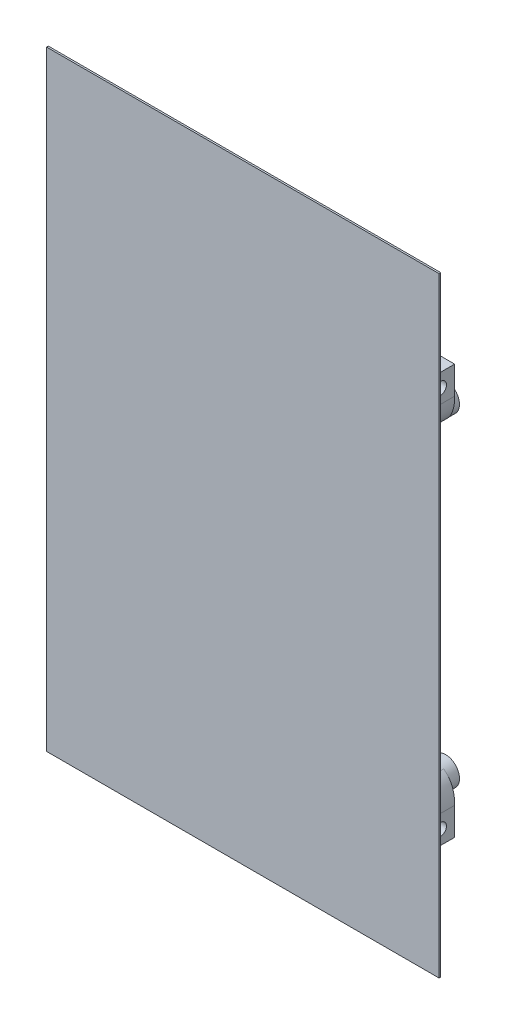
SolidWorks part; units mm, degrees
ref_plane "Front Plane" through (0, 0, 0) normal (0, 0, 1) x (1, 0, 0)
ref_plane "Top Plane" through (0, 0, 0) normal (0, 1, 0) x (1, 0, 0)
ref_plane "Right Plane" through (0, 0, 0) normal (1, 0, 0) x (0, 0, -1)
sketch "Sketch1" plane through (0, 0, 0) normal (0, 0, 1) x (1, 0, 0)
  line L1 (109, 161.3091) -> (-4, 161.3091)
  line L2 (109, 161.3091) -> (109, -14.3091)
  line L3 (109, -14.3091) -> (-4, -14.3091)
  line L4 (-4, 161.3091) -> (-4, -14.3091)
extrude "Boss-Extrude1" add sketch "Sketch1" along normal blind 0.5
sketch "Sketch2" plane through (0, 0, 0) normal (0, 0, -1) x (-1, 0, 0)
  circle A0 centre (-5.6, 26.85) radius 2 construction
  circle A1 centre (-99.4, 26.85) radius 2 construction
  circle A2 centre (-99.4, 120.15) radius 2 construction
  circle A3 centre (-5.6, 120.15) radius 2 construction
  circle A4 centre (-5.6, 26.85) radius 2
  circle A5 centre (-99.4, 26.85) radius 2
  circle A6 centre (-99.4, 120.15) radius 2
  circle A7 centre (-5.6, 120.15) radius 2
  circle A8 centre (-5.6, 120.15) radius 4
  circle A9 centre (-5.6, 26.85) radius 4
  circle A10 centre (-99.4, 26.85) radius 4
  circle A11 centre (-99.4, 120.15) radius 4
  dimension "D1" = 8
extrude "Boss-Extrude2" add sketch "Sketch2" along normal up to surface (11 mm away)
sketch "Sketch3" plane through (0, 0, 0) normal (0, 0, -1) x (-1, 0, 0)
  line L0 (-99.4, 120.15) -> (-5.6, 120.15) construction
  line L1 (-7.3321, 123.15) -> (-8.2458, 123.15)
  line L2 (-9.0641, 120.15) -> (-7.3321, 117.15)
  line L3 (-7.3321, 117.15) -> (-3.8679, 117.15)
  line L4 (-3.8679, 117.15) -> (-2.1359, 120.15)
  line L5 (-2.1359, 120.15) -> (-3.8679, 123.15)
  line L6 (-3.8679, 123.15) -> (-7.3321, 123.15)
  line L7 (-7.3321, 123.15) -> (-9.0641, 120.15)
  line L8 (-7.3321, 117.15) -> (-8.2458, 117.15)
  line L9 (-52.5, 161.3091) -> (-52.5, -14.3091) construction
  line L10 (-109, 161.3091) -> (4, 161.3091) construction
  line L11 (4, -14.3091) -> (-109, -14.3091) construction
  line L12 (-97.6679, 117.15) -> (-96.7542, 117.15)
  line L13 (-97.6679, 123.15) -> (-95.9359, 120.15)
  line L14 (-95.9359, 120.15) -> (-97.6679, 117.15)
  line L15 (-97.6679, 117.15) -> (-101.1321, 117.15)
  line L16 (-101.1321, 117.15) -> (-102.8641, 120.15)
  line L17 (-102.8641, 120.15) -> (-101.1321, 123.15)
  line L18 (-101.1321, 123.15) -> (-97.6679, 123.15)
  line L19 (-97.6679, 123.15) -> (-96.7542, 123.15)
  line L20 (-109, 73.5) -> (4, 73.5) construction
  line L21 (-109, -14.3091) -> (-109, 161.3091) construction
  line L22 (4, 161.3091) -> (4, -14.3091) construction
  line L23 (-7.3321, 29.85) -> (-8.2458, 29.85)
  line L24 (-7.3321, 29.85) -> (-3.8679, 29.85)
  line L25 (-9.0641, 26.85) -> (-7.3321, 29.85)
  line L26 (-2.1359, 26.85) -> (-3.8679, 23.85)
  line L27 (-3.8679, 29.85) -> (-2.1359, 26.85)
  line L28 (-7.3321, 23.85) -> (-9.0641, 26.85)
  line L29 (-3.8679, 23.85) -> (-7.3321, 23.85)
  line L30 (-7.3321, 23.85) -> (-8.2458, 23.85)
  line L31 (-97.6679, 23.85) -> (-96.7542, 23.85)
  line L32 (-101.1321, 23.85) -> (-97.6679, 23.85)
  line L33 (-102.8641, 26.85) -> (-101.1321, 23.85)
  line L34 (-101.1321, 29.85) -> (-102.8641, 26.85)
  line L35 (-97.6679, 29.85) -> (-101.1321, 29.85)
  line L36 (-95.9359, 26.85) -> (-97.6679, 29.85)
  line L37 (-97.6679, 23.85) -> (-95.9359, 26.85)
  line L38 (-97.6679, 29.85) -> (-96.7542, 29.85)
  circle A0 centre (-5.6, 120.15) radius 3 construction
  circle A1 centre (-5.6, 120.15) radius 4 construction
  circle A2 centre (-5.6, 120.15) radius 4 construction
  circle M15 centre (-99.4, 120.15) radius 4
  circle M16 centre (-99.4, 26.85) radius 4
  circle M17 centre (-5.6, 26.85) radius 4
  circle M18 centre (-5.6, 120.15) radius 4
  dimension "D1" = 6
extrude "Cut-Extrude1" cut sketch "Sketch3" along normal blind 3 contours L18 L17 L16 L15 L14 L13 | L19 L13 L14 L12 M15 | L6 L7 L2 L3 L4 L5 | L8 L2 L7 L1 M18 | L29 L26 L27 L24 L25 L28 | L30 L28 L25 L23 M17 | L32 L37 L36 L35 L34 L33 | L38 L36 L37 L31 M16 region at (8.2536, 121.6821, 0) region at (5.6, 120.15, 0) region at (96.7464, 118.6179, 0) region at (99.4, 120.15, 0) region at (8.2536, 28.3821, 0) region at (5.6, 26.85, 0) region at (96.7464, 25.3179, 0) region at (99.4, 26.85, 0)
sketch "Sketch4" plane through (0, 0, 0) normal (0, 0, -1) x (-1, 0, 0)
  line L0 (-105, -14.3091) -> (-105, 12.5) construction
  line L1 (-105, 14.5) -> (-100, 14.5)
  line L2 (-105, 14.5) -> (-105, 22.5)
  line L3 (-105, 22.5) -> (-100, 22.5)
  line L4 (-100, 14.5) -> (-100, 22.5)
  line L5 (-100, 18.5) -> (-105, 18.5) construction
  line L7 (-104.2951, 26.85) -> (-99.4, 26.85) construction
  line L8 (-100, 22.5) -> (-100, 22.8953)
  line L15 (-109, 18.5) -> (-105, 18.5) construction
  arc A0 (-96.7542, 29.85) -> (-96.7542, 23.85) centre (-99.4, 26.85) ccw construction
  circle A1 centre (-99.4, 26.85) radius 4 construction
  spline S1 degree 3 poles (-105, 22.5) (-105, 25.5429) (-104.3608, 28.0669) (-101.8496, 30.0122) knots 0 0 0 0 1 1 1 1
  point P8 (-100, 23.3244)
  point P26 (-100, 21.1429)
  point P27 (0, 0)
  point P28 (-99.2, 17.1247)
  arc M10 (-96.7542, 23.85) -> (-96.7542, 29.85) centre (-99.4, 26.85) cw
  dimension "D1" = 8
  dimension "D2" = 5
extrude "Boss-Extrude3" add sketch "Sketch4" along normal blind 8 contours L1 L4 L3 L2 | S1 L3 L8 M10 region at (102.5, 18.5, 0) region at (103.3471, 24.4202, 0)
sketch "Sketch5" plane through (100, 0, 0) normal (-1, 0, 0) x (0, 0, 1)
  circle A1 centre (-3.8964, 18.5) radius 1.75
  circle A2 centre (-3.8964, 18.5) radius 2.9 construction
  dimension "D1" = 3.5
extrude "Cut-Extrude2" cut sketch "Sketch5" against normal up to next
sketch "Sketch6" plane through (100, 0, 0) normal (-1, 0, 0) x (0, 0, 1)
  line L1 (-3.8964, 21.9641) -> (-6.8964, 20.2321)
  line L2 (-6.8964, 20.2321) -> (-6.8964, 16.7679)
  line L3 (-6.8964, 16.7679) -> (-3.8964, 15.0359)
  line L4 (-3.8964, 15.0359) -> (-0.8964, 16.7679)
  line L5 (-0.8964, 16.7679) -> (-0.8964, 20.2321)
  line L6 (-0.8964, 20.2321) -> (-3.8964, 21.9641)
  circle A0 centre (-3.8964, 18.5) radius 3 construction
  dimension "D1" = 6
extrude "Cut-Extrude3" cut sketch "Sketch6" against normal blind 2.5
ref_plane "Plane1" through (0, 73.5, 0) normal (0, -1, 0) x (-1, 0, 0)
ref_plane "Plane2" through (52.5, 0, 0) normal (-1, 0, 0) x (0, 0, 1)
mirror "Mirror1" about plane through (52.5, 0, 0) normal (-1, 0, 0) of "Cut-Extrude3", "Cut-Extrude2", "Boss-Extrude3"
mirror "Mirror2" about plane through (0, 73.5, 0) normal (0, -1, 0) of "Cut-Extrude3", "Cut-Extrude2", "Boss-Extrude3", "Mirror1"
sketch "Sketch7" plane through (0, 0, 0) normal (0, 0, -1) x (-1, 0, 0)
  line L0 (-109, 73.5) -> (4, 73.5) construction
  line L1 (-109, -14.3091) -> (-109, 161.3091) construction
  line L2 (4, 161.3091) -> (4, -14.3091) construction
  line L3 (-52.5, -14.3091) -> (-52.5, 161.3091) construction
  line L4 (0, -14.3091) -> (-105, -14.3091) construction
  line L5 (0, 161.3091) -> (-105, 161.3091) construction
  line L6 (-109, -14.3091) -> (4, 161.3091) construction
  line L7 (4, -14.3091) -> (-109, 161.3091) construction
  line L8 (-91.1065, 13.5) -> (-13.8935, 13.5) construction
  line L9 (-91.1065, 133.5) -> (-13.8935, 133.5) construction
  line L10 (-91.1065, 13.5) -> (-91.1065, 133.5) construction
  line L11 (-13.8935, 13.5) -> (-13.8935, 133.5) construction
  line L12 (-93.6065, 11) -> (-11.3935, 11)
  line L13 (-11.3935, 11) -> (-11.3935, 136)
  line L14 (-93.6065, 136) -> (-11.3935, 136)
  line L15 (-93.6065, 11) -> (-93.6065, 136)
  line L16 (-109, 71) -> (4, 71)
  line L17 (6.1024, -12.9563) -> (-106.8976, 162.6619)
  line L18 (-50, -14.3091) -> (-50, 161.3091)
  line L19 (-106.8976, -15.6619) -> (6.1024, 159.9563)
  line L20 (-88.6065, 16) -> (-16.3935, 16)
  line L21 (-16.3935, 16) -> (-16.3935, 131)
  line L22 (-88.6065, 131) -> (-16.3935, 131)
  line L23 (-88.6065, 16) -> (-88.6065, 131)
  line L24 (-109, 76) -> (4, 76)
  line L25 (1.8976, -15.6619) -> (-111.1024, 159.9563)
  line L26 (-55, -14.3091) -> (-55, 161.3091)
  line L27 (-111.1024, -12.9563) -> (1.8976, 162.6619)
  dimension "D1" = 60
  dimension "D2" = 2.5
  dimension "D3" = 2.5
extrude "Boss-Extrude4" add sketch "Sketch7" along normal blind 0.5 contours L12 L26 L20 L19 | L27 L15 L12 L19 L20 L23 | L15 L27 L23 L16 | L27 L23 L20 L19 L26 L16 | L24 L15 L16 L23 | L16 L27 L25 L24 L23 | L23 L25 L15 L24 | L25 L23 L22 L17 L14 L15 | L24 L26 L17 L22 L23 L25 | L22 L26 L14 L17 | L26 L22 L18 L14 | L17 L27 L18 L22 L26 | L22 L27 L14 L18 | L27 L22 L21 L19 L13 L14 | L27 L18 L24 L19 L21 L22 | L21 L24 L13 L19 | L24 L21 L16 L13 | L24 L19 L17 L16 L21 | L21 L17 L13 L16 | L25 L20 L21 L17 L16 L18 | L26 L20 L18 L25 L19 | L26 L12 L18 L20 | L12 L25 L20 L18 | L25 L12 L13 L17 L21 L20 | L26 L19 L25 L16 | L27 L16 L26 L25 | L26 L16 L25 | L25 L27 L26 L24 | L27 L25 L26 | L26 L27 L24 | L24 L27 L17 L26 | L27 L17 L24 L18 | L24 L18 L17 L19 | L19 L18 L16 L17 | L19 L16 L18 | L25 L18 L16 L19 | L25 L19 L16 | L27 L26 L25 L16 L19 L18 L17 L24 | L27 L24 L17 | L24 L17 L18 | L18 L19 L17 region at (90.4529, 15.002, 0) region at (71.5799, 13.4595, 0) region at (91.1677, 44.5125, 0) region at (52.5, 13.5, 0) region at (71.8032, 43.5, 0) region at (91.1065, 73.5, 0) region at (33.4201, 13.4595, 0) region at (52.5, 41.4809, 0) region at (54.1143, 68.5681, 0) region at (91.1677, 102.4875, 0) region at (72.4385, 73.5, 0) region at (55.7555, 71.9147, 0) region at (14.5471, 15.002, 0) region at (52.5, 70.2933, 0) region at (50.8857, 68.5681, 0) region at (54.6214, 71.5884, 0) region at (90.4529, 131.998, 0) region at (55.1576, 73.5, 0) region at (55.7555, 75.0853, 0) region at (33.1968, 43.5, 0) region at (50.3786, 71.5884, 0) region at (52.5, 73.5, 0) region at (71.8032, 103.5, 0) region at (54.6214, 75.4116, 0) region at (13.8323, 44.5125, 0) region at (49.2445, 71.9147, 0) region at (49.8424, 73.5, 0) region at (71.5799, 133.5405, 0) region at (54.1143, 78.4319, 0) region at (52.5, 76.7067, 0) region at (13.8935, 73.5, 0) region at (32.5615, 73.5, 0) region at (49.2445, 75.0853, 0) region at (50.3786, 75.4116, 0) region at (52.5, 133.5, 0) region at (52.5, 105.5191, 0) region at (50.8857, 78.4319, 0) region at (13.8323, 102.4875, 0) region at (33.1968, 103.5, 0) region at (33.4201, 133.5405, 0) region at (14.5471, 131.998, 0)
